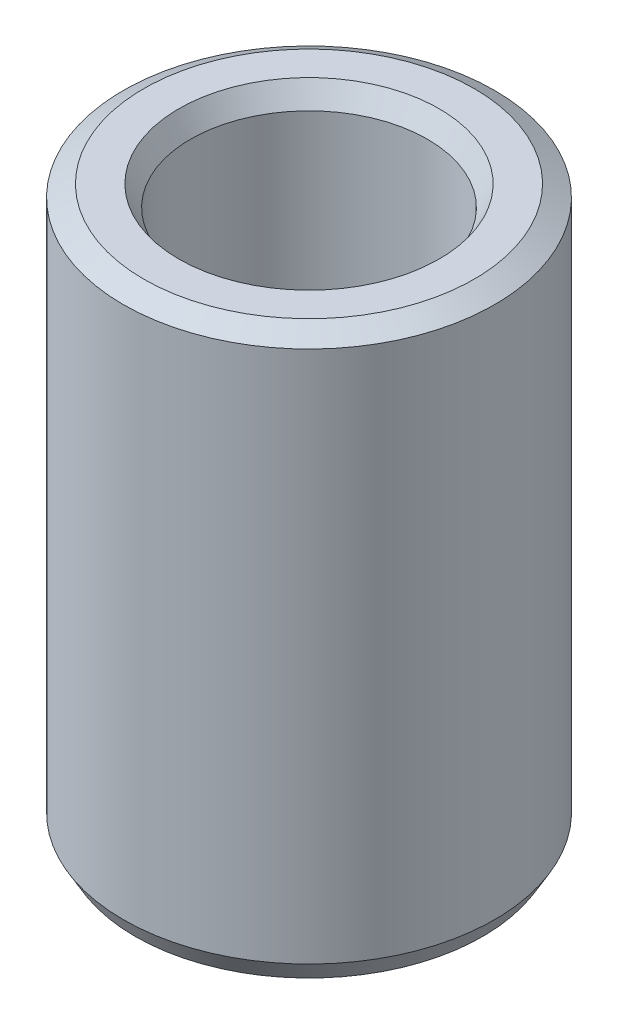
SolidWorks part; units mm, degrees
ref_plane "Front Plane" through (0, 0, 0) normal (0, 0, 1) x (1, 0, 0)
ref_plane "Top Plane" through (0, 0, 0) normal (0, 1, 0) x (1, 0, 0)
ref_plane "Right Plane" through (0, 0, 0) normal (1, 0, 0) x (0, 0, -1)
sketch "Sketch1" plane through (0, 0, 0) normal (0, 1, 0) x (1, 0, 0)
  circle A0 centre (0, 0) radius 60
  dimension "SLEEVE_OD" = 120
extrude "Boss-Extrude1" add sketch "Sketch1" along normal blind 182.6127
sketch "Sketch2" plane through (0, 0, 0) normal (0, 1, 0) x (1, 0, 0)
  circle A0 centre (0, 0) radius 38.2779
  dimension "BORE_D" = 76.5557
extrude "Cut-Extrude1" cut sketch "Sketch2" along normal through all
chamfer "Chamfer1" distance 3.8165 angle 60 4 edges at (0, 182.6127, 38.2779) (0, 0, 38.2779) (0, 0, 60) (0, 182.6127, 60) first distance on face at (0, 182.6127, 38.2779) first distance on face at (0, 0, 38.2779) first distance on face at (0, 182.6127, 60)
